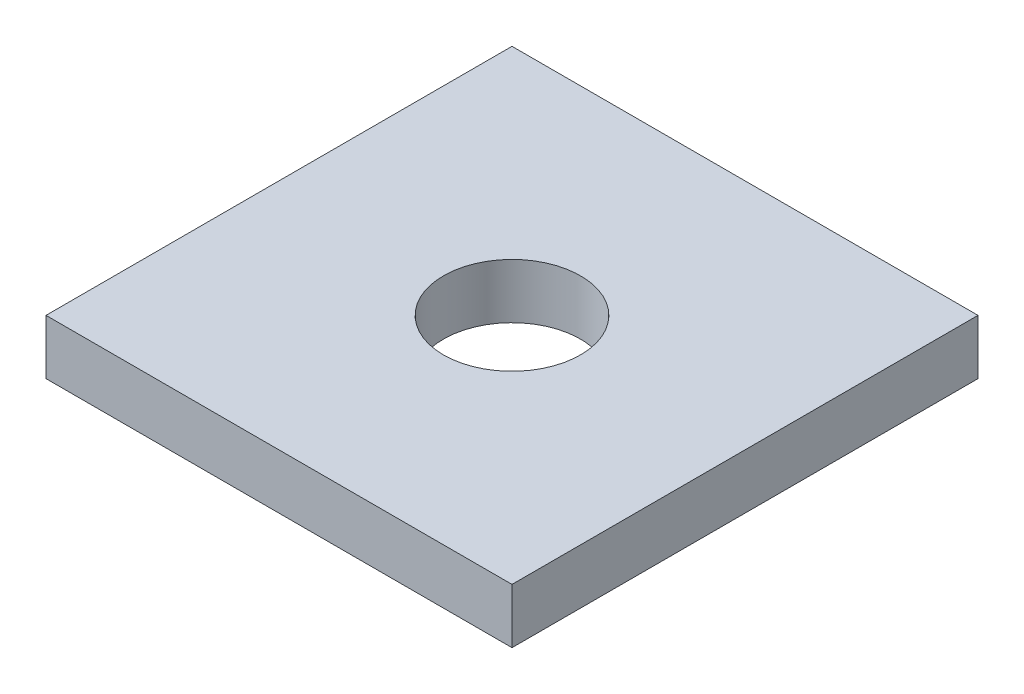
SolidWorks part; units mm, degrees
ref_plane "Front Plane" through (0, 0, 0) normal (0, 0, 1) x (1, 0, 0)
ref_plane "Top Plane" through (0, 0, 0) normal (0, 1, 0) x (1, 0, 0)
ref_plane "Right Plane" through (0, 0, 0) normal (1, 0, 0) x (0, 0, -1)
sketch "Sketch1" plane through (0, 0, 0) normal (0, 1, 0) x (1, 0, 0)
  line L1 (170, 170) -> (-170, 170)
  line L2 (170, 170) -> (170, -170)
  line L3 (170, -170) -> (-170, -170)
  line L4 (-170, 170) -> (-170, -170)
  line L5 (170, 170) -> (-170, -170) construction
  line L6 (170, -170) -> (-170, 170) construction
  point P0 (0, 0)
  dimension "D1" = 340
  dimension "D2" = 340
extrude "base" add sketch "Sketch1" along normal blind 40 contours L1 L4 L3 L2
sketch "Sketch2" plane through (0, 40, 0) normal (0, 1, 0) x (1, 0, 0)
  circle A0 centre (0, 0) radius 50
  dimension "D1" = 100
extrude "actuator cut" cut sketch "Sketch2" against normal blind 40
